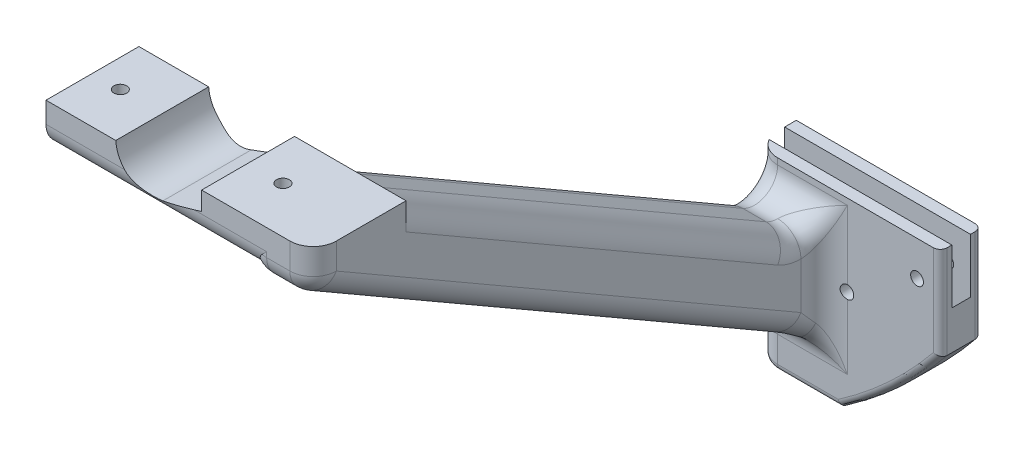
SolidWorks part; units mm, degrees
ref_plane "前视基准面" through (0, 0, 0) normal (0, 0, 1) x (1, 0, 0)
ref_plane "上视基准面" through (0, 0, 0) normal (0, 1, 0) x (1, 0, 0)
ref_plane "右视基准面" through (0, 0, 0) normal (1, 0, 0) x (0, 0, -1)
other "Configuration Table"
sketch "草图1" plane through (0, 0, 0) normal (0, 0, 1) x (1, 0, 0)
  line L1 (80, 80) -> (80, 0)
  line L2 (80, 0) -> (0, 0)
  line L3 (0, 0) -> (0, 80)
  line L4 (0, 80) -> (80, 80)
  dimension "D1" = 80
  dimension "D2" = 80
extrude "凸台-拉伸1" add sketch "草图1" along normal blind 5
sketch "草图3" plane through (80, 0, 0) normal (1, 0, 0) x (0, 0, -1)
  line L0 (-5, 20) -> (-225, 147.0171)
  line L1 (-5, 0) -> (-5, 80) construction
  line L2 (-225, 147.0171) -> (-225, 165)
  line L3 (-185, 165) -> (-225, 165)
  line L4 (-185, 165) -> (-185, 163.923)
  line L5 (-185, 163.923) -> (-5, 60)
  line L6 (-5, 60) -> (-5, 20)
  line L7 (0, 0) -> (0, 80) construction
  point P10 (0, 40)
  dimension "D1" = 40
  dimension "D2" = 40
  dimension "D3" = 20
  dimension "D4" = 180
  dimension "D5" = 60
  dimension "D6" = 165
extrude "凸台-拉伸2" add sketch "草图3" against normal blind 30 from offset 50 offset against normal yes
sketch "草图4" plane through (0, 0, 225) normal (0, 0, 1) x (1, 0, 0)
  line L0 (0, 145) -> (-85, 145)
  line L1 (0, 165) -> (0, 147.0171) construction
  line L2 (-85, 145) -> (-85, 165)
  line L3 (-85, 165) -> (0, 165)
  line L4 (0, 165) -> (0, 145)
  dimension "D1" = 20
  dimension "D2" = 85
extrude "凸台-拉伸3" add sketch "草图4" against normal blind 40
sketch "草图5" plane through (0, 0, 225) normal (0, 0, 1) x (1, 0, 0)
  line L0 (-85, 165) -> (30, 165) construction
  line L1 (-35.6447, 150.6462) -> (-18, 156)
  line L2 (-18, 156) -> (-18, 165)
  line L3 (30, 165) -> (30, 147.0171) construction
  line L4 (-55, 165) -> (-18, 165)
  arc A0 (-55, 165) -> (-35.6447, 150.6462) centre (-40, 165) ccw
  dimension "D1" = 30
  dimension "D2" = 9
  dimension "D3" = 22
  dimension "D4" = 70
extrude "切除-拉伸1" cut sketch "草图5" against normal through all
sketch "草图6" plane through (0, 0, 5) normal (0, 0, 1) x (1, 0, 0)
  line L0 (0, 0) -> (80, 0) construction
  line L1 (80, 0) -> (80, 80) construction
  line L2 (80, 39.8441) -> (80, 0)
  line L3 (80, 0) -> (37.0265, 0)
  circle A0 centre (-76, 165) radius 190 construction
  arc A1 (37.0265, 0) -> (80, 39.8441) centre (-76, 165) ccw
  circle A2 centre (-76, 165) radius 200 construction
  dimension "D1" = 165
  dimension "D3" = 380
  dimension "D2" = 156
  dimension "D4" = 10
extrude "切除-拉伸2" cut sketch "草图6" against normal blind 10
sketch "草图7" plane through (0, 0, 0) normal (0, 0, -1) x (-1, 0, 0)
  line L0 (-80, 39.8441) -> (-80, 80) construction
  line L1 (0, 0) -> (-37.0265, 0) construction
  line L2 (-80, 39.8441) -> (-80, 56.538)
  line L4 (-80, 56.538) -> (-80, 80)
  line L5 (-37.0265, 0) -> (0, 0)
  line L6 (0, 0) -> (0, 15)
  line L7 (0, 80) -> (0, 0) construction
  line L8 (0, 15) -> (-40.619, 15)
  arc A0 (-80, 39.8441) -> (-37.0265, 0) centre (76, 165) ccw construction
  arc A1 (-80, 39.8441) -> (-37.0265, 0) centre (76, 165) ccw
  arc A2 (-80, 56.538) -> (-40.619, 15) centre (76, 165) ccw
  dimension "D1" = 156
  dimension "D3" = 380
  dimension "D2" = 165
  dimension "D4" = 15
extrude "凸台-拉伸6" add sketch "草图7" along normal blind 8 contours L2 A1 L5 L6 L8 A2
sketch "草图9" plane through (0, 0, -8) normal (0, 0, -1) x (-1, 0, 0)
  line L0 (0, 0) -> (0, 15) construction
  line L1 (-37.0265, 0) -> (0, 0) construction
  line L2 (-80, 39.8441) -> (-80, 56.538) construction
  line L3 (-80, 56.538) -> (-80, 80) construction
  line L4 (-80, 80) -> (0, 80) construction
  line L5 (0, 80) -> (0, 15) construction
  line L6 (0, 0) -> (0, 15)
  line L7 (-37.0265, 0) -> (0, 0)
  line L8 (-80, 39.8441) -> (-80, 56.538)
  line L9 (-80, 56.538) -> (-80, 80)
  line L10 (-80, 80) -> (0, 80)
  line L11 (0, 80) -> (0, 15)
  arc A0 (-80, 39.8441) -> (-37.0265, 0) centre (76, 165) ccw construction
  arc A1 (-80, 39.8441) -> (-37.0265, 0) centre (76, 165) ccw
extrude "凸台-拉伸7" add sketch "草图9" along normal blind 5
sketch "草图10" plane through (0, 0, 5) normal (0, 0, 1) x (1, 0, 0)
  line L0 (80, 80) -> (0, 80) construction
  line L1 (40, 65) -> (70, 65) construction
  line L2 (40, 65) -> (40, 45) construction
  line L3 (40, 45) -> (70, 45) construction
  line L4 (70, 65) -> (70, 45) construction
  line L5 (80, 39.8441) -> (80, 80) construction
  circle A0 centre (70, 65) radius 2.75
  circle A2 centre (40, 45) radius 2.75
  dimension "D5" = 5.5
  dimension "D1" = 20
  dimension "D2" = 30
  dimension "D3" = 15
  dimension "D4" = 10
extrude "切除-拉伸3" cut sketch "草图10" against normal through all
fillet "圆角1" radius 10 1 edges at (30, 40, 5)
fillet "圆角2" radius 10 1 edges at (20, 20, 5)
fillet "圆角4" radius 10 2 edges at (-42.5, 145, 185) (-42.5, 145, 225)
fillet "圆角6" radius 10 1 edges at (15, 147.0171, 225)
fillet "圆角7" radius 10 4 edges at (0, 153.8953, 225) (0, 7.1132, 5) (0, 19.2265, 6.3397) (0, 83.5085, 115)
fillet "圆角8" radius 10 1 edges at (20, 60, 5)
fillet "圆角9" radius 10 11 edges at (30, 158.8953, 225) (30, 147.7906, 223.6603) (35, 19.2265, 6.3397) (30.3407, 24.2792, 12.4118) (32.9289, 70.2494, 7.9289) (30, 67.6612, 17.5882) (0, 78.6603, 5) (0, 68.6603, 10) (30, 84.9519, 117.5) (30, 116.2917, 102.5) (0, 116.2917, 102.5)
sketch "草图15" plane through (0, 145, 0) normal (0, -1, 0) x (1, 0, 0)
  line L0 (-85, 225) -> (-51.1803, 225) construction
  line L1 (-85, 195) -> (-85, 215) construction
  circle A0 centre (-73, 205) radius 2.75
  dimension "D1" = 5.5
  dimension "D2" = 20
  dimension "D3" = 12
extrude "切除-拉伸5" cut sketch "草图15" against normal through all
sketch "草图16" plane through (0, 145, 0) normal (0, -1, 0) x (1, 0, 0)
  circle A0 centre (-73, 205) radius 6
  dimension "D1" = 12
extrude "切除-拉伸6" cut sketch "草图16" against normal blind 6
sketch "草图17" plane through (0, 145, 0) normal (0, -1, 0) x (1, 0, 0)
  line L0 (-85, 195) -> (-85, 215) construction
  line L1 (-21.2957, 225) -> (10, 225) construction
  circle A0 centre (-3, 205) radius 2.75
  dimension "D1" = 82
  dimension "D3" = 5.5
  dimension "D2" = 20
extrude "切除-拉伸7" cut sketch "草图17" against normal through all
sketch "草图18" plane through (0, 145, 0) normal (0, -1, 0) x (1, 0, 0)
  circle A0 centre (-3, 205) radius 6
  dimension "D1" = 12
extrude "切除-拉伸9" cut sketch "草图18" against normal blind 6 and the other way through all
fillet "圆角11" radius 3 8 edges at (0, 0, -9) (2.9289, 0, 2.0711) (80, 59.922, 5) (80, 59.922, -13) (59.9805, 18.3395, 5) (59.9805, 18.3395, -13) (18.5133, 0, -13) (23.5133, 0, 5)
sketch "草图19" plane through (0, 165, 0) normal (0, 1, 0) x (1, 0, 0)
  line L1 (-97.812, -157.9286) -> (48.4426, -157.9286)
  line L2 (-97.812, -157.9286) -> (-97.812, -247.982)
  line L3 (-97.812, -247.982) -> (48.4426, -247.982)
  line L4 (48.4426, -157.9286) -> (48.4426, -247.982)
extrude "切除-拉伸10" cut sketch "草图19" against normal blind 1
